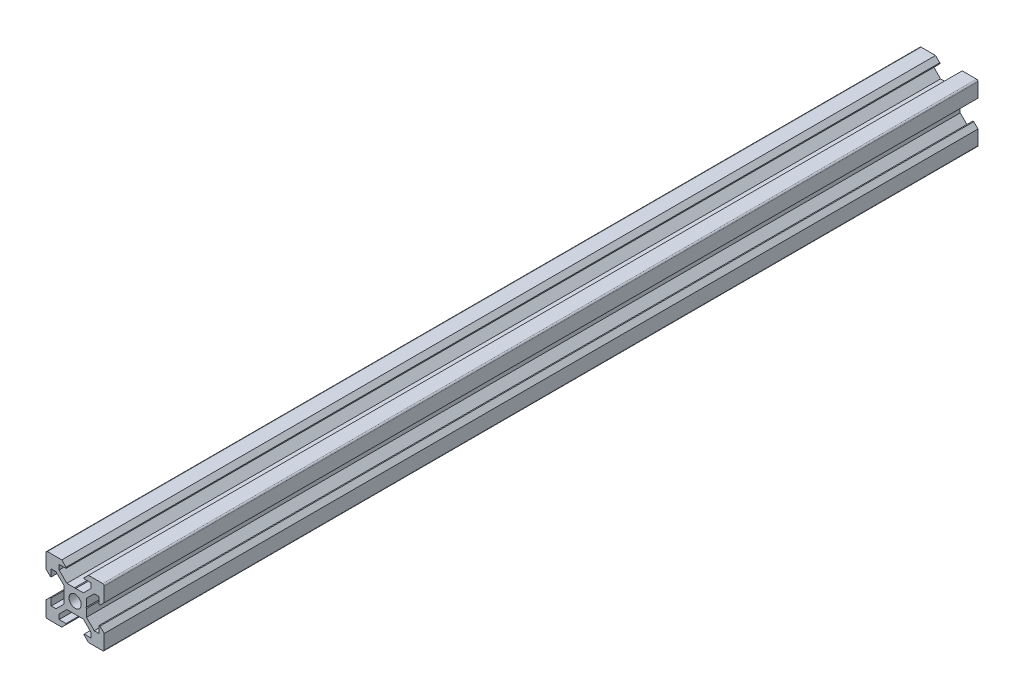
SolidWorks part; units mm, degrees
ref_plane "Plan de face" through (0, 0, 0) normal (0, 0, 1) x (1, 0, 0)
ref_plane "Plan de dessus" through (0, 0, 0) normal (0, 1, 0) x (1, 0, 0)
ref_plane "Plan de droite" through (0, 0, 0) normal (1, 0, 0) x (0, 0, -1)
ref_axis "Axe" through (0, 0, -13.782) along (0, 0, 1)
sketch "Esquisse1" plane through (0, 0, 0) normal (0, 0, 1) x (1, 0, 0)
  line L0 (0, 22.8977) -> (0, -22.8977) construction
  line L1 (-33.6074, 0) -> (33.6074, 0) construction
  line L2 (0, 0) -> (-22.2114, 22.2114) construction
  line L3 (-9.5, 10) -> (-4.58, 10)
  line L4 (-4.58, 10) -> (-3.125, 8.545)
  line L5 (-3.125, 8.545) -> (-3.125, 8.2)
  line L6 (-3.125, 8.2) -> (-5.5, 8.2)
  line L7 (-2.8393, 3.9) -> (-5.5, 6.5607)
  line L8 (-2.8393, 3.9) -> (-0.21, 3.9)
  line L9 (-5.5, 6.5607) -> (-5.5, 8.2)
  line L10 (0, 3.69) -> (0, 2.1)
  line L11 (-3.9, 2.8393) -> (-6.5607, 5.5)
  line L12 (-8.545, 3.125) -> (-8.2, 3.125)
  line L13 (-8.2, 3.125) -> (-8.2, 5.5)
  line L14 (-6.5607, 5.5) -> (-8.2, 5.5)
  line L15 (-10, 4.58) -> (-8.545, 3.125)
  line L16 (-10, 9.5) -> (-10, 4.58)
  line L17 (-0.21, 3.9) -> (0, 3.69)
  line L18 (-3.9, 2.8393) -> (-3.9, 0.21)
  line L19 (-3.69, 0) -> (-2.1, 0)
  line L20 (-3.9, 0.21) -> (-3.69, 0)
  arc A0 (-2.1, 0) -> (0, 2.1) centre (0, 0) cw
  arc A1 (-9.5, 10) -> (-10, 9.5) centre (-9.5, 9.5) ccw
  point P4 (0, 0)
  point P7 (0, 0)
  point P30 (-10, 10)
  dimension "D5" = 11
  dimension "D2" = 2.1
  dimension "D3" = 6.25
  dimension "D10" = 0.5
  dimension "D4" = 9.16
  dimension "D6" = 1.5
  dimension "D7" = 1.8
  dimension "D8" = 4.3
  dimension "D9" = 20
  dimension "D11" = 0.42
extrude "Boss.-Extru.1" add sketch "Esquisse1" along normal blind 300
sketch "Esquisse3" plane through (0, 0, 300) normal (0, 0, 1) x (1, 0, 0)
  line L0 (0, 0) -> (-9.8536, 9.8536) construction
  line L1 (-8.2, 8.2) -> (-8.2, 6.57)
  line L2 (-8.2, 6.57) -> (-7.54, 6.57)
  line L3 (-7.54, 6.57) -> (-6.57, 7.54)
  line L4 (-8.2, 3.125) -> (-8.2, 5.5) construction
  line L5 (-6.57, 8.2) -> (-6.57, 7.54)
  line L6 (-8.2, 8.2) -> (-6.57, 8.2)
  line L7 (-5.5, 6.5607) -> (-5.5, 8.2) construction
  arc A0 (-9.5, 10) -> (-10, 9.5) centre (-9.5, 9.5) ccw construction
  point P13 (-7.055, 7.055)
  point P14 (-6.57, 7.87)
  dimension "D1" = 1.07
extrude "Enlèv. mat.-Extru.1" [suppressed] cut sketch "Esquisse3" against normal through all
pattern_circular "Répétition circulaire1" count 4 every 90 about axis through (0, 0, -13.782) along (0, 0, 1) of "Boss.-Extru.1", "Enlèv. mat.-Extru.1"
